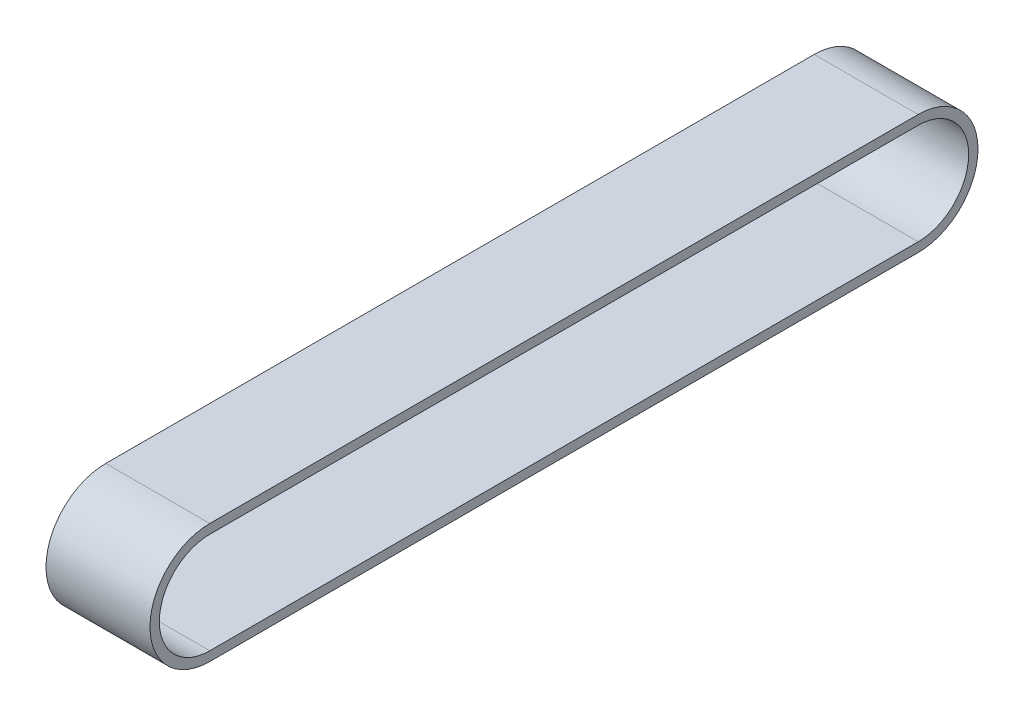
SolidWorks part; units mm, degrees
material "PUR"
ref_plane "Front" through (0, 0, 0) normal (0, 0, 1) x (1, 0, 0)
ref_plane "Top" through (0, 0, 0) normal (0, 1, 0) x (1, 0, 0)
ref_plane "Right" through (0, 0, 0) normal (1, 0, 0) x (0, 0, -1)
sketch "Sketch1" plane through (0, 0, 0) normal (1, 0, 0) x (0, 0, -1)
  line L0 (-86.5187, 0) -> (86.5187, 0) construction
  line L1 (-86.5187, 14.605) -> (86.5187, 14.605)
  line L2 (-86.5187, -14.605) -> (86.5187, -14.605)
  line L3 (-86.5187, 0) -> (86.5187, 0) construction
  line L4 (-86.5187, 12.319) -> (86.5187, 12.319)
  line L5 (-86.5187, -12.319) -> (86.5187, -12.319)
  arc A0 (-86.5187, 14.605) -> (-86.5187, -14.605) centre (-86.5187, 0) ccw
  arc A1 (86.5187, -14.605) -> (86.5187, 14.605) centre (86.5187, 0) ccw
  arc A2 (-86.5187, 12.319) -> (-86.5187, -12.319) centre (-86.5187, 0) ccw
  arc A3 (86.5187, -12.319) -> (86.5187, 12.319) centre (86.5187, 0) ccw
  point P2 (0, 0)
  point P9 (0, 0)
  dimension "D2" = 24.638
  dimension "D1" = 2.286
  dimension "D3" = 173.0375
extrude "Boss-Extrude1" add sketch "Sketch1" along normal mid plane 25.4
